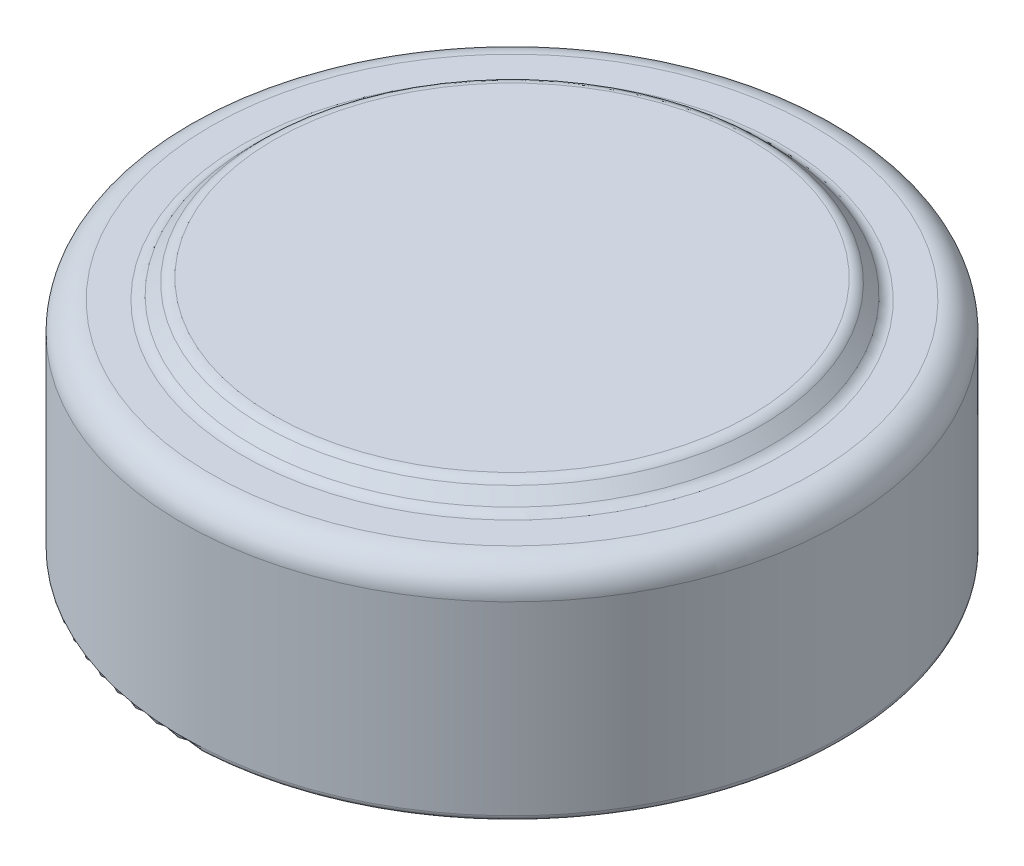
SolidWorks part; units mm, degrees
ref_plane "Front Plane" through (0, 0, 0) normal (0, 0, 1) x (1, 0, 0)
ref_plane "Top Plane" through (0, 0, 0) normal (0, 1, 0) x (1, 0, 0)
ref_plane "Right Plane" through (0, 0, 0) normal (1, 0, 0) x (0, 0, -1)
sketch "Sketch1" plane through (0, 0, 0) normal (0, 0, 1) x (1, 0, 0)
  line L0 (0, 0) -> (-5.7, 0)
  line L1 (-5.8, 0.1) -> (-5.8, 3.36)
  line L2 (-4.1964, 4.2) -> (0, 4.2)
  line L3 (0, 4.2) -> (0, 0)
  line L4 (-4.3732, 4.1268) -> (-4.5668, 3.9332)
  line L7 (-5.3, 3.86) -> (-4.7436, 3.86)
  arc A0 (-5.8, 3.36) -> (-5.3, 3.86) centre (-5.3, 3.36) cw
  arc A1 (-4.3732, 4.1268) -> (-4.1964, 4.2) centre (-4.1964, 3.95) cw
  arc A2 (-4.7436, 3.86) -> (-4.5668, 3.9332) centre (-4.7436, 4.11) ccw
  arc A3 (-5.7, 0) -> (-5.8, 0.1) centre (-5.7, 0.1) cw
  point P9 (-5.8, 3.86)
  point P14 (-4.3, 4.2)
  point P17 (-5.8, 0)
  point P18 (-4.64, 3.86)
  dimension "D6" = 0.5
  dimension "D7" = 0.25
  dimension "D8" = 0.1
  dimension "D1" = 5.8
  dimension "D2" = 4.2
  dimension "D3" = 4.64
  dimension "D4" = 3.86
  dimension "D5" = 45
revolve "Revolve1" add sketch "Sketch1" angle 360 about L3
sketch "Sketch2" plane through (0, 0, 0) normal (0, -1, 0) x (1, 0, 0)
  line L0 (0.25, 0.25) -> (2, 0.25)
  line L1 (-0.25, 2) -> (0.25, 2)
  line L2 (-0.25, 2) -> (-0.25, 0.25)
  line L3 (-0.25, -2) -> (0.25, -2)
  line L4 (0.25, 2) -> (0.25, 0.25)
  line L5 (-2, 0.25) -> (-0.25, 0.25)
  line L6 (-2, 0.25) -> (-2, -0.25)
  line L7 (-2, -0.25) -> (-0.25, -0.25)
  line L8 (2, 0.25) -> (2, -0.25)
  line L9 (0.25, -0.25) -> (2, -0.25)
  line L10 (0.25, -0.25) -> (0.25, -2)
  line L11 (-0.25, -0.25) -> (-0.25, -2)
  circle A0 centre (0, 0) radius 4 construction
  text T0 "                                 LR43" font "Century Gothic" height 1
  dimension "D1" = 8
  dimension "D2" = 0.5
  dimension "D3" = 0.5
  dimension "D4" = 0.25
  dimension "D5" = 0.25
  dimension "D6" = 4
  dimension "D7" = 4
  dimension "D8" = 2
  dimension "D9" = 2
wrap "Wrap1" sketch "Sketch2" wrap type scribe source sketch "Sketch2" face at (-5.7, 0, 0)
